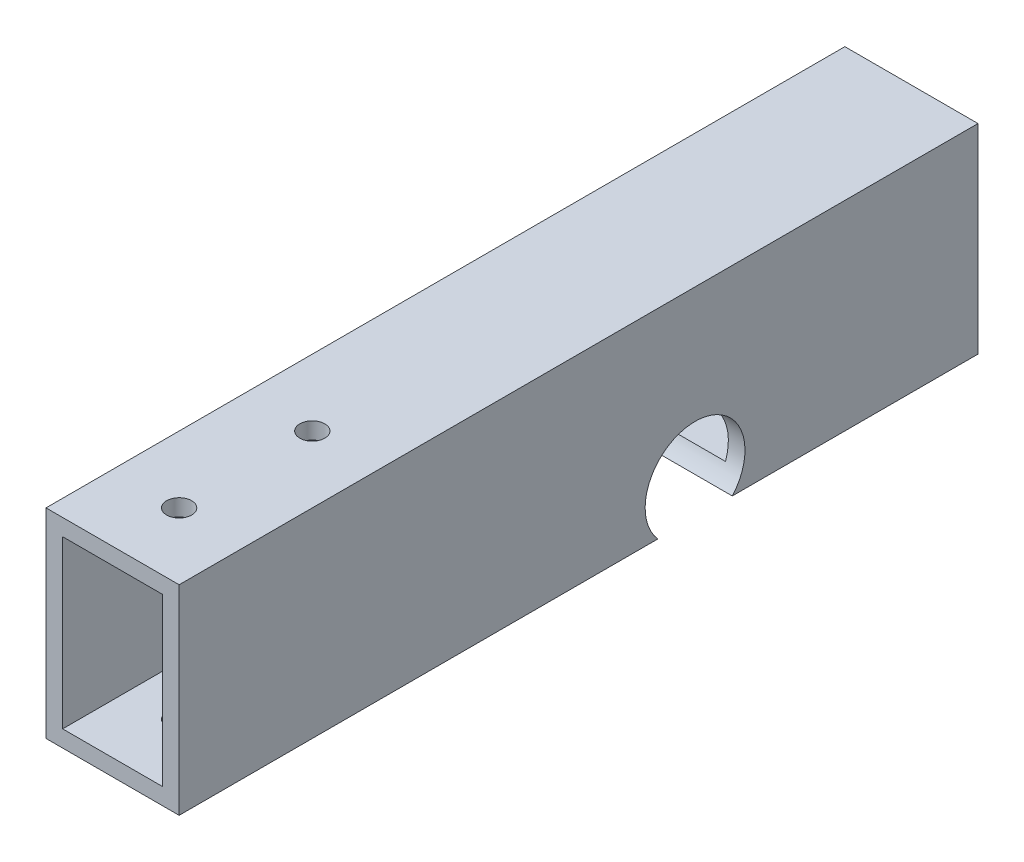
SolidWorks part; units mm, degrees
material "6063-T1"
ref_plane "Front Plane" through (0, 0, 0) normal (0, 0, 1) x (1, 0, 0)
ref_plane "Top Plane" through (0, 0, 0) normal (0, 1, 0) x (1, 0, 0)
ref_plane "Right Plane" through (0, 0, 0) normal (1, 0, 0) x (0, 0, -1)
sketch "Sketch1" plane through (0, 0, 0) normal (0, 0, 1) x (1, 0, 0)
  line L1 (-12.7, 19.05) -> (12.7, 19.05)
  line L2 (-12.7, 19.05) -> (-12.7, -19.05)
  line L3 (-12.7, -19.05) -> (12.7, -19.05)
  line L4 (12.7, 19.05) -> (12.7, -19.05)
  line L5 (-12.7, 19.05) -> (12.7, -19.05) construction
  line L6 (-12.7, -19.05) -> (12.7, 19.05) construction
  point P0 (0, 0)
  dimension "D1" = 25.4
  dimension "D2" = 38.1
extrude "Boss-Extrude1" add sketch "Sketch1" along normal blind 152.4
shell "Shell1" thickness 3.175 removed face at (0, 0, 0) removed face at (0, 0, 152.4)
sketch "Sketch2" plane through (12.7, 0, 0) normal (1, 0, 0) x (0, 0, -1)
  line L0 (-152.4, -19.05) -> (0, -19.05) construction
  line L1 (0, -19.05) -> (0, 19.05) construction
  circle A0 centre (-53.975, -12.7) radius 9.525
  dimension "D1" = 19.05
  dimension "D2" = 6.35
  dimension "D3" = 53.975
extrude "Cut-Extrude1" cut sketch "Sketch2" against normal through all
sketch "Sketch3" plane through (0, 19.05, 0) normal (0, 1, 0) x (1, 0, 0)
  line L0 (12.7, -152.4) -> (-12.7, -152.4) construction
  circle A0 centre (0, -139.7) radius 2.3812
  circle A1 centre (0, -114.3) radius 2.3812
  dimension "D1" = 4.7625
  dimension "D3" = 4.7625
  dimension "D2" = 12.7
  dimension "D4" = 25.4
extrude "Cut-Extrude2" cut sketch "Sketch3" against normal through all
